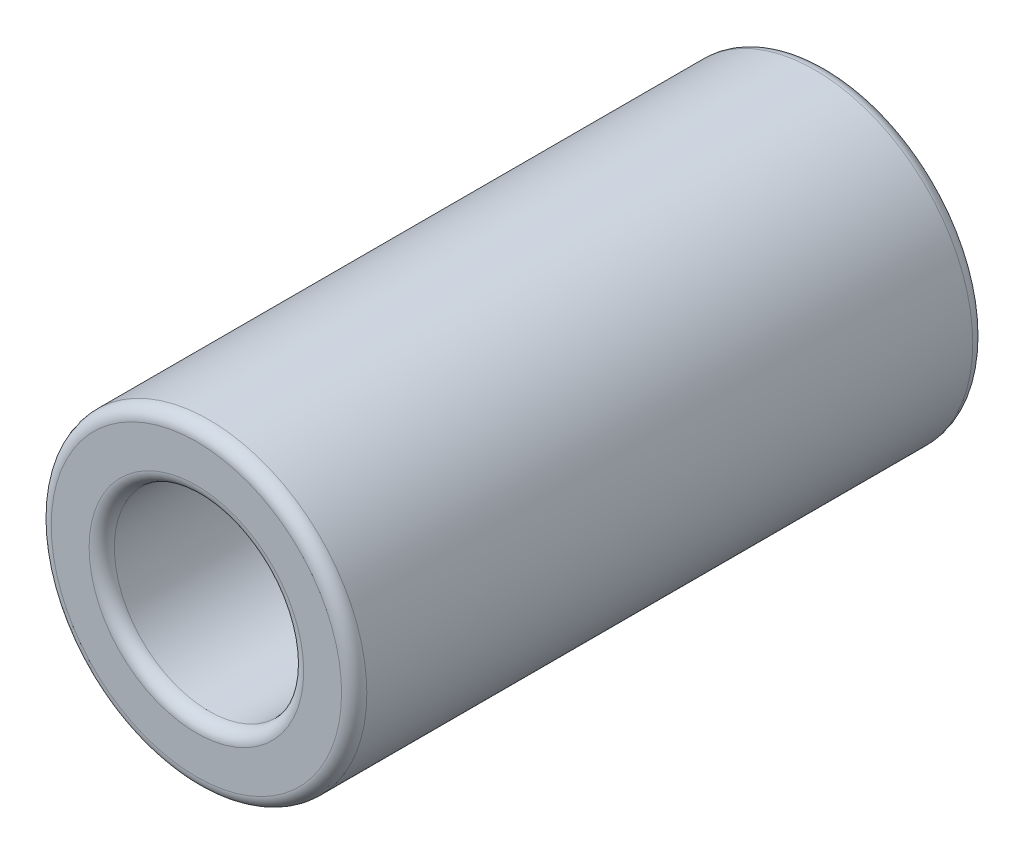
SolidWorks part; units mm, degrees
ref_plane "Front Plane" through (0, 0, 0) normal (0, 0, 1) x (1, 0, 0)
ref_plane "Top Plane" through (0, 0, 0) normal (0, 1, 0) x (1, 0, 0)
ref_plane "Right Plane" through (0, 0, 0) normal (1, 0, 0) x (0, 0, -1)
sketch "Sketch1" plane through (0, 0, 0) normal (0, 0, 1) x (1, 0, 0)
  circle A0 centre (0, 0) radius 2.5
  circle A1 centre (0, 0) radius 1.5
  dimension "D1" = 5
  dimension "D2" = 3
extrude "Boss-Extrude1" add sketch "Sketch1" along normal blind 10
fillet "Fillet1" radius 0.2 4 edges at (2.5, 0, 0) (1.5, 0, 0) (1.5, 0, 10) (2.5, 0, 10)
ref_axis "Axis1" through (0, 0, 9.8) along (0, 0, -1)
